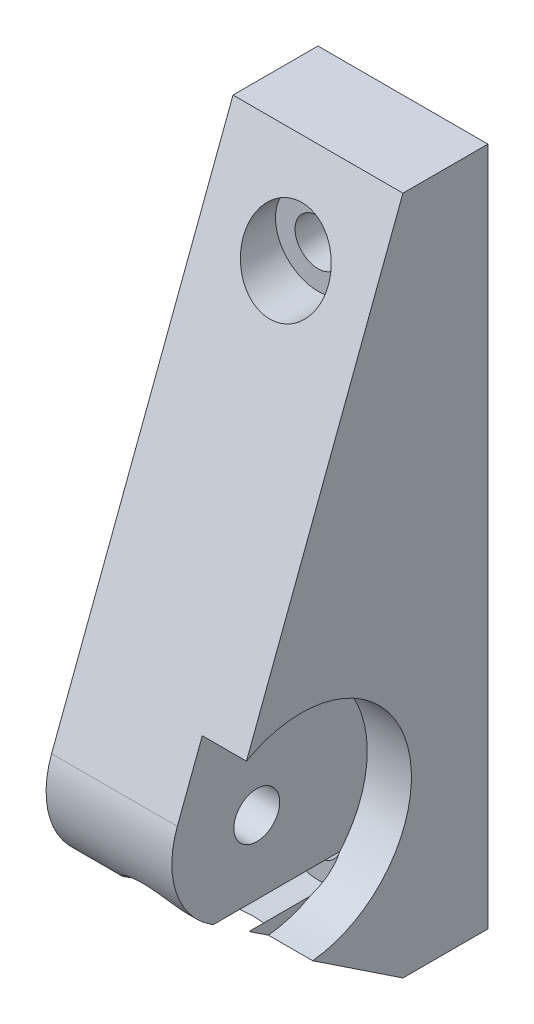
SolidWorks part; units mm, degrees
material "ABS"
ref_plane "xy" through (0, 0, 0) normal (0, 0, 1) x (1, 0, 0)
ref_plane "xz" through (0, 0, 0) normal (0, 1, 0) x (1, 0, 0)
ref_plane "yz" through (0, 0, 0) normal (1, 0, 0) x (0, 0, -1)
ref_axis "x" through (-11, 0, 0) along (1, 0, 0)
ref_axis "y" through (0, 14, 0) along (0, -1, 0)
ref_axis "z" through (0, 0, -1.65) along (0, 0, 1)
sketch "Sketch1" plane through (0, 0, 0) normal (0, 0, 1) x (1, 0, 0)
  line L0 (0, -18.15) -> (0, 18.15) construction
  line L1 (-10, 10) -> (10, 10)
  line L2 (-10, 10) -> (-10, -70)
  line L3 (-10, -70) -> (10, -70)
  line L4 (10, 10) -> (10, -70)
  circle A0 centre (0, 0) radius 2.7
  circle A1 centre (0, -60) radius 2.7
  point P7 (0, 10)
  dimension "D1" = 5.4
  dimension "D2" = 10
  dimension "D3" = 20
  dimension "D4" = 80
  dimension "D5" = 10
extrude "Boss-Extrude1" add sketch "Sketch1" along normal blind 10
sketch "Sketch2" plane through (0, 0, 0) normal (1, 0, 0) x (0, 0, -1)
  line L0 (-10, 10) -> (-31.3535, -46.4626)
  line L1 (-27.5409, -58.3246) -> (-10, -70)
  line L2 (-10, -70) -> (-10, 10)
  line L3 (0, 11) -> (0, -11) construction
  arc A0 (-31.3535, -46.4626) -> (-27.5409, -58.3246) centre (-22, -50) ccw
  circle A1 centre (-22, -50) radius 2.7
  dimension "D1" = 5.4
  dimension "D2" = 10
  dimension "D3" = 10
  dimension "D4" = 22
extrude "Boss-Extrude2" add sketch "Sketch2" along normal mid plane 20
sketch "Sketch3" plane through (0, 0, 10) normal (0, 0, -1) x (-1, 0, 0)
  circle A0 centre (0, -60) radius 5
  circle A1 centre (0, 0) radius 5
  dimension "D1" = 10
extrude "Cut-Extrude1" cut sketch "Sketch3" against normal through all
sketch "Sketch4" plane through (10, 0, 0) normal (1, 0, 0) x (0, 0, -1)
  circle A0 centre (-22, -50) radius 13
  dimension "D1" = 26
extrude "Cut-Extrude2" cut sketch "Sketch4" against normal blind 5.2
